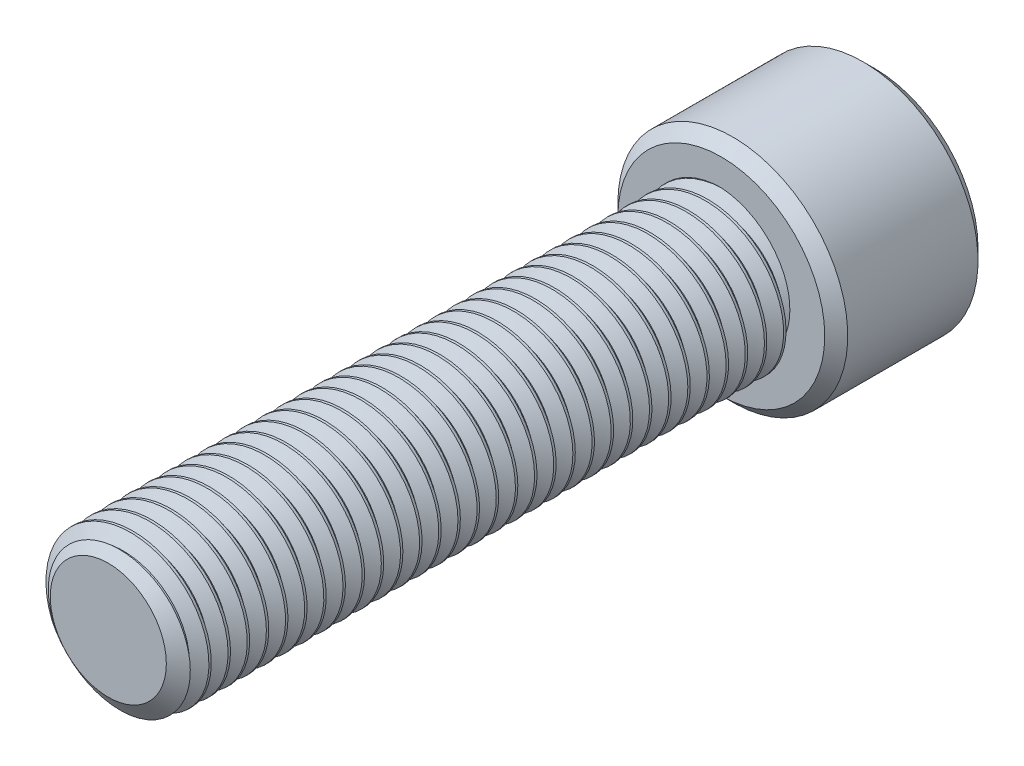
SolidWorks part; units mm, degrees
other "DetailItem1"
ref_plane "Front Plane" through (0, 0, 0) normal (0, 0, 1) x (1, 0, 0)
ref_plane "Top Plane" through (0, 0, 0) normal (0, 1, 0) x (1, 0, 0)
ref_plane "Right Plane" through (0, 0, 0) normal (1, 0, 0) x (0, 0, -1)
sketch "Sketch1" plane through (0, 0, 0) normal (0, 0, 1) x (1, 0, 0)
  circle A0 centre (0, 0) radius 3.175
  dimension "OD" = 6.35
extrude "Extrude1" add sketch "Sketch1" against normal blind 25.4
sketch "Sketch2" plane through (0, 0, 0) normal (0, 0, 1) x (1, 0, 0)
  circle A0 centre (0, 0) radius 3.175 construction
  circle A1 centre (0, 0) radius 3.175
curve "Helix/Spiral1" pitch 0.7937 height 26.1937 turns 33 parameters "pitch"=0.7937
sketch "Sketch3" plane through (0, 0, 0) normal (1, 0, 0) x (0, 0, -1)
  line L0 (-0.6945, 3.175) -> (-0.3969, 2.6594)
  line L1 (-0.3969, 2.6594) -> (-0.2977, 2.6594)
  line L2 (-0.2977, 2.6594) -> (0, 3.175)
  line L3 (-0.6945, 3.175) -> (0, 3.175)
  line L4 (-0.3473, 3.175) -> (-0.3473, 2.6594) construction
  line L5 (-0.5457, 2.9172) -> (-0.1488, 2.9172) construction
  line L6 (0, 3.175) -> (0, -3.175) construction
  dimension "D1" = 0.0992
  dimension "D2" = 0.3969
  dimension "D3" = 60
sweep "Cut-Sweep1" cut profiles "Sketch3" path "Helix/Spiral1"
sketch "Sketch4" plane through (0, 0, 0) normal (1, 0, 0) x (0, 0, -1)
  line L0 (0.5388, 3.175) -> (0, 2.4054)
  line L1 (0, 2.4054) -> (0, 3.175)
  line L2 (0.5388, 3.175) -> (0, 3.175)
  line L3 (-0.6945, 3.175) -> (0, 3.175) construction
  line L4 (0, 0) -> (7.0209, 0) construction
  dimension "D1" = 55
  dimension "D2" = 0.254
revolve "Cut-Revolve1" cut sketch "Sketch4" angle 360 about L4
sketch "Sketch5" plane through (0, 0, 0) normal (1, 0, 0) x (0, 0, -1)
  line L0 (25.4, -2.6671) -> (25.4, 2.2654) construction
  line L1 (25.4, 3.302) -> (0.1202, 3.302)
  line L2 (25.4, 3.302) -> (25.4, 0)
  line L3 (25.4, 0) -> (0, 0)
  line L4 (0, 2.9718) -> (0, 0)
  line L5 (0.1202, 3.302) -> (0, 2.9718)
  line L6 (0, 0) -> (9.9695, 0) construction
  point P3 (0, 3.302)
  point P10 (0, 3.302)
  dimension "D1" = 0.3302
  dimension "D2" = 0.127
  dimension "D3" = 20
  dimension "Min Thread" = 0
revolve "partially thread" [suppressed] add sketch "Sketch5" angle 360 about L6
sketch "Sketch6" plane through (0, 0, -25.4) normal (0, 0, -1) x (-1, 0, 0)
  circle A0 centre (0, 0) radius 4.7625
  dimension "head dia" = 9.525
extrude "Extrude2" add sketch "Sketch6" along normal blind 6.35
sketch "Sketch7" plane through (0, 0, -31.75) normal (0, 0, -1) x (-1, 0, 0)
  line L1 (0, 2.7496) -> (-2.3813, 1.3748)
  line L2 (-2.3813, 1.3748) -> (-2.3813, -1.3748)
  line L3 (-2.3813, -1.3748) -> (0, -2.7496)
  line L4 (0, -2.7496) -> (2.3813, -1.3748)
  line L5 (2.3813, -1.3748) -> (2.3813, 1.3748)
  line L6 (2.3813, 1.3748) -> (0, 2.7496)
  circle A0 centre (0, 0) radius 2.3813 construction
  dimension "hex dia" = 4.7625
extrude "Cut-Extrude1" cut sketch "Sketch7" against normal blind 3.5719
sketch "Sketch8" plane through (0, 0, -31.75) normal (0, 0, -1) x (-1, 0, 0)
  circle A0 centre (0, 0) radius 2.7496
extrude "Cut-Extrude2" cut sketch "Sketch8" against normal through all draft 45
chamfer "Chamfer1" distance 0.4763 angle 45 2 edges at (-4.7625, 0, -31.75) (-4.7625, 0, -25.4)
sketch "Sketch9" plane through (0, 0, 0) normal (1, 0, 0) x (0, 0, -1)
  line L0 (0, 3.175) -> (0, -3.175) construction
  line L1 (1.9844, 3.175) -> (1.9844, -3.175) construction
  dimension "D1" = 1.9844
equation "\"D3@Helix/Spiral1\" = \"screw length@Extrude1\"+\"pitch@Helix/Spiral1\""
equation "\"D1@Sketch3\" = \"pitch@Helix/Spiral1\"*.125"
equation "\"D2@Sketch3\" = \"pitch@Helix/Spiral1\"*.5"
equation "\"D1@Cut-Extrude1\" = \"hex dia@Sketch7\"*.75"
equation "\"D1@Chamfer1\" = \"head dia@Sketch6\"*.05"
equation "\"D1@Sketch9\" = \"pitch@Helix/Spiral1\"*2.5"
